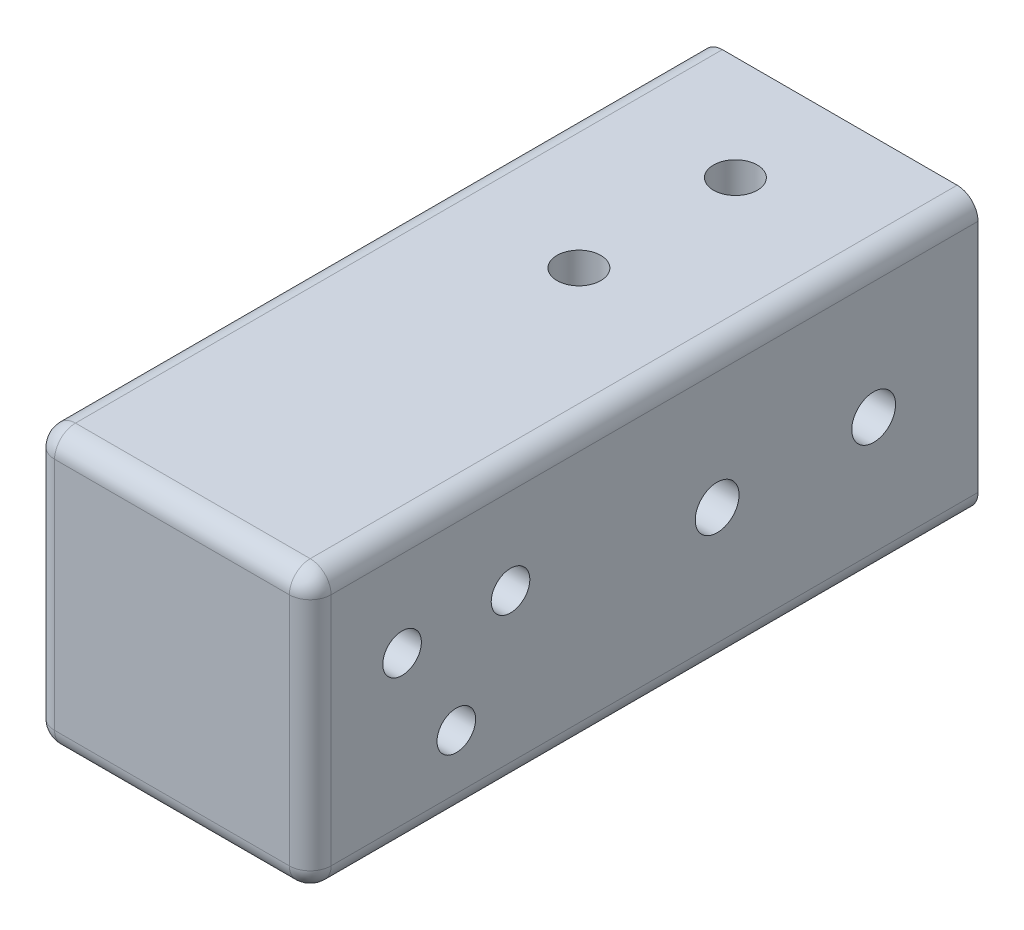
SolidWorks part; units mm, degrees
ref_plane "前视基准面" through (0, 0, 0) normal (0, 0, 1) x (1, 0, 0)
ref_plane "上视基准面" through (0, 0, 0) normal (0, 1, 0) x (1, 0, 0)
ref_plane "右视基准面" through (0, 0, 0) normal (1, 0, 0) x (0, 0, -1)
other "Configuration Table"
sketch "草图1" plane through (0, 0, 0) normal (0, 0, 1) x (1, 0, 0)
  line L0 (-13.25, 13.25) -> (13.25, 13.25)
  line L1 (-10.25, -10.25) -> (10.25, -10.25)
  line L2 (-10.25, -10.25) -> (-10.25, 10.25)
  line L3 (-10.25, 10.25) -> (10.25, 10.25)
  line L4 (10.25, -10.25) -> (10.25, 10.25)
  line L5 (-10.25, -10.25) -> (10.25, 10.25) construction
  line L6 (-10.25, 10.25) -> (10.25, -10.25) construction
  line L7 (13.25, -13.25) -> (13.25, 13.25)
  line L8 (-13.25, -13.25) -> (13.25, -13.25)
  line L9 (-13.25, -13.25) -> (-13.25, 13.25)
  point P0 (0, 0)
  dimension "D1" = 20.5
  dimension "D2" = 20.5
  dimension "D3" = 3
extrude "凸台-拉伸1" add sketch "草图1" along normal blind 40
sketch "草图3" plane through (0, 0, 40) normal (0, 0, 1) x (1, 0, 0)
  line L1 (-13.25, -13.25) -> (13.25, -13.25)
  line L2 (-13.25, -13.25) -> (-13.25, 13.25)
  line L3 (-13.25, 13.25) -> (13.25, 13.25)
  line L4 (13.25, -13.25) -> (13.25, 13.25)
  line L5 (-13.25, -13.25) -> (13.25, 13.25) construction
  line L6 (-13.25, 13.25) -> (13.25, -13.25) construction
  point P0 (0, 0)
extrude "凸台-拉伸2" add sketch "草图3" along normal blind 20
sketch "草图9" plane through (0, 0, 60) normal (0, 0, 1) x (1, 0, 0)
  line L1 (-13.25, 13.25) -> (13.25, 13.25)
  line L2 (-13.25, 13.25) -> (-13.25, -13.25)
  line L3 (-13.25, -13.25) -> (13.25, -13.25)
  line L4 (13.25, 13.25) -> (13.25, -13.25)
extrude "凸台-拉伸5" add sketch "草图9" along normal blind 4
sketch "草图10" plane through (13.25, 0, 0) normal (1, 0, 0) x (0, 0, -1)
  line L0 (-64, 0) -> (-60, 0)
  line L1 (-64, -13.25) -> (-64, 13.25) construction
  line L2 (-60, 0) -> (-50, 0)
  circle A0 centre (-50, 0) radius 10
  circle A1 centre (-50, 0) radius 12
  dimension "D3" = 20
  dimension "D1" = 4
  dimension "D2" = 10
  dimension "D4" = 2
extrude "凸台-拉伸7" add sketch "草图10" along normal blind 4
sketch "草图12" plane through (-13.25, 0, 0) normal (-1, 0, 0) x (0, 0, 1)
  line L0 (64, 0) -> (60, 0)
  line L1 (64, 13.25) -> (64, -13.25) construction
  circle A0 centre (50, 0) radius 10
  circle A1 centre (50, 0) radius 12
  dimension "D2" = 20
  dimension "D1" = 4
  dimension "D3" = 10
  dimension "D4" = 2
extrude "凸台-拉伸8" add sketch "草图12" along normal blind 4
sketch "草图13" plane through (-13.25, 0, 0) normal (-1, 0, 0) x (0, 0, 1)
  circle A0 centre (50, 0) radius 6
  circle A1 centre (50, 6) radius 1.85
  circle A2 centre (55.1962, 3) radius 1.85
  circle A3 centre (55.1962, -3) radius 1.85
  circle A4 centre (50, -6) radius 1.85
  circle A5 centre (44.8038, -3) radius 1.85
  circle A6 centre (44.8038, 3) radius 1.85
  dimension "D1" = 12
  dimension "D2" = 3.7
  dimension "D3" = 6
extrude "切除-拉伸3" cut sketch "草图13" against normal through all contours A6 | A2 | A4
sketch "草图14" plane through (0, -13.25, 0) normal (0, -1, 0) x (1, 0, 0)
  line L0 (0, 0) -> (0, 10)
  line L1 (0, 10) -> (0, 25)
  circle A1 centre (0, 10) radius 2.1
  circle A2 centre (0, 25) radius 2.1
  dimension "D2" = 4.2
  dimension "D4" = 4.2
  dimension "D3" = 15
  dimension "D1" = 10
sketch "草图15" plane through (13.25, 0, 0) normal (1, 0, 0) x (0, 0, -1)
  line L0 (0, 0) -> (-10, 0)
  line L1 (-10, 0) -> (-25, 0)
  circle A0 centre (-10, 0) radius 2.1
  circle A1 centre (-25, 0) radius 2.1
  dimension "D2" = 4.2
  dimension "D4" = 4.2
  dimension "D1" = 10
  dimension "D3" = 15
extrude "切除-拉伸5" cut sketch "草图15" against normal through all
extrude "切除-拉伸6" cut sketch "草图14" against normal through all
sketch "草图16" plane through (13.25, 0, 0) normal (1, 0, 0) x (0, 0, -1)
  circle A0 centre (-50, 0) radius 10.4669
  dimension "D1" = 20.9338
sketch "草图18" plane through (13.25, 0, 0) normal (1, 0, 0) x (0, 0, -1)
  circle A0 centre (-50, 0) radius 12
extrude "切除-拉伸9" cut sketch "草图18" along normal blind 4
sketch "草图19" plane through (-13.25, 0, 0) normal (-1, 0, 0) x (0, 0, 1)
  circle A0 centre (50, 0) radius 12
extrude "切除-拉伸11" cut sketch "草图19" along normal blind 4
fillet "圆角6" radius 2 3 edges at (0, -13.25, 64) (13.25, -13.25, 32) (-13.25, -13.25, 32)
fillet "圆角7" radius 2 3 edges at (13.25, 1, 64) (12.6642, -12.6642, 63.4142) (13.25, 13.25, 32)
fillet "圆角8" radius 2 3 edges at (-1, 13.25, 64) (12.6642, 12.6642, 63.4142) (-13.25, 13.25, 32)
fillet "圆角9" radius 2 3 edges at (-12.6642, -12.6642, 63.4142) (-13.25, 0, 64) (-12.6642, 12.6642, 63.4142)
